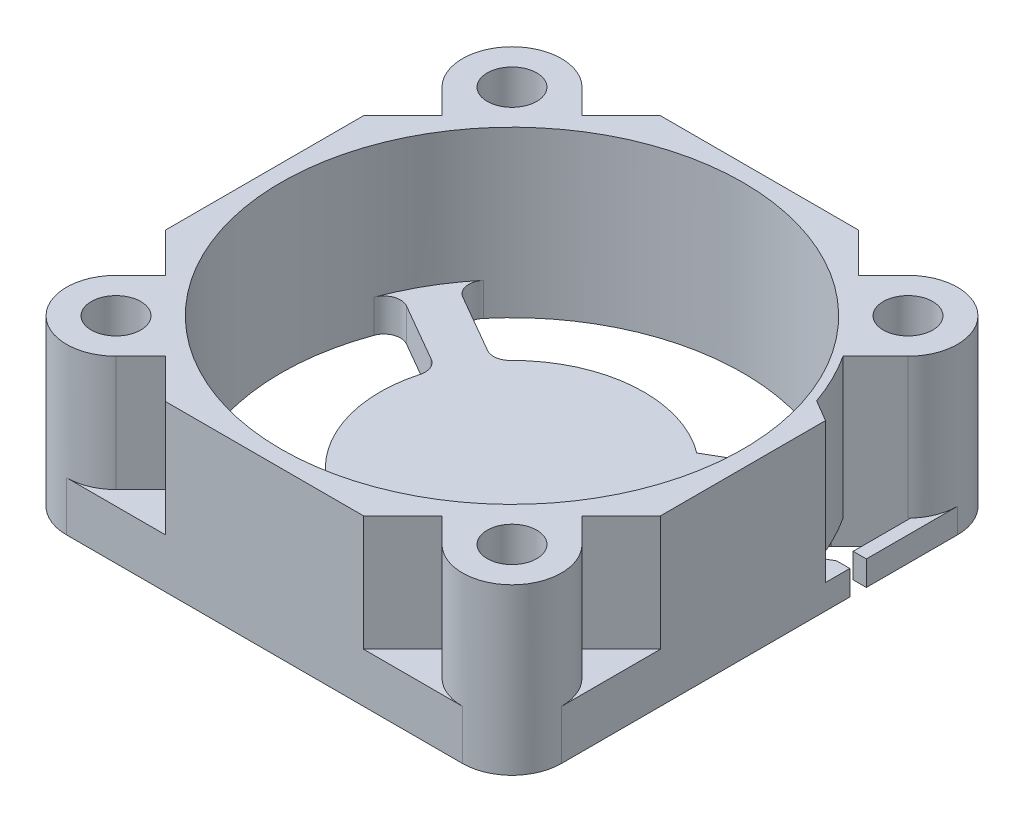
SolidWorks part; units mm, degrees
ref_plane "前基準面" through (0, 0, 0) normal (0, 0, 1) x (1, 0, 0)
ref_plane "上基準面" through (0, 0, 0) normal (0, 1, 0) x (1, 0, 0)
ref_plane "右基準面" through (0, 0, 0) normal (1, 0, 0) x (0, 0, -1)
sketch "Sketch2" plane through (0, 0, 0) normal (0, 1, 0) x (1, 0, 0)
  line L1 (-15, -15) -> (15, -15)
  line L2 (-15, -15) -> (-15, 15)
  line L3 (-15, 15) -> (15, 15)
  line L4 (15, -15) -> (15, 15)
  line L5 (-15, -15) -> (15, 15) construction
  line L6 (-15, 15) -> (15, -15) construction
  point P0 (0, 0)
  dimension "D1" = 30
extrude "Boss-Extrude1" add sketch "Sketch2" along normal blind 10
sketch "Sketch3" plane through (0, 10, 0) normal (0, 1, 0) x (1, 0, 0)
  line L0 (15, -15) -> (15, 15) construction
  line L1 (15, 15) -> (-15, 15) construction
  line L2 (12, 15) -> (15, 15) construction
  line L3 (15, 15) -> (15, 12) construction
  line L10 (9.8787, 14.1213) -> (8.3787, 12.6213)
  line L11 (12, 12) -> (15, 12) construction
  line L12 (12, 12) -> (12, 15) construction
  line L13 (12, 15) -> (15, 15) construction
  line L14 (15, 12) -> (15, 15) construction
  line L15 (8.3787, 12.6213) -> (6, 15)
  line L16 (6, 15) -> (12, 15)
  line L17 (15, 15) -> (0, 0) construction
  line L18 (15, 6) -> (15, 12)
  line L19 (12.6213, 8.3787) -> (15, 6)
  line L20 (14.1213, 9.8787) -> (12.6213, 8.3787)
  circle A0 centre (12, 12) radius 1.5
  circle A9 centre (0, 0) radius 14
  arc A10 (9.6266, 10.1651) -> (10.1651, 9.6266) centre (12, 12) ccw
  arc A11 (14.1213, 9.8787) -> (9.8787, 14.1213) centre (12, 12) ccw
  circle A12 centre (12, 12) radius 3 construction
  point P16 (15, 12)
  line M5 (15, -15) -> (15, 15)
  line M6 (15, 15) -> (-15, 15)
  dimension "D1" = 3
  dimension "D3" = 3
  dimension "D5" = 6
  dimension "D4" = 1.5
  dimension "D2" = 28
extrude "Cut-Extrude1" cut sketch "Sketch3" against normal through all contours A10 A9 | A11 M5 M6 | A0 region at (14.3299, 10, -14.3299) region at (12, 10, -12) region at (-0.0002, 10, 0.0002)
extrude "Cut-Extrude5" cut sketch "Sketch3<3>" against normal blind 7 contours A11 L20 L19 M5 | A11 L15 L10 M6 region at (14.2274, 10, -8.4599) region at (8.4599, 10, -14.2274)
sketch "Sketch3<3>" plane through (0, 10, 0) normal (0, 1, 0) x (1, 0, 0) same geometry as "Sketch3"
pattern_circular "CirPattern2" count 4 every 90 about axis through (0, 0, 0) along (0, 1, 0) of "Cut-Extrude1", "Cut-Extrude5"
sketch "Sketch5" plane through (0, 0, 0) normal (0, -1, 0) x (1, 0, 0)
  line L0 (-1.25, 7.9017) -> (-1.25, 13.9441)
  line L1 (1.25, 7.9017) -> (1.25, 13.9441)
  line L2 (-1.25, 7.9017) -> (1.25, 7.9017)
  line L3 (-6.2181, -5.0334) -> (-11.4509, -8.0546)
  line L4 (-7.4681, -2.8683) -> (-12.7009, -5.8895)
  line L5 (-6.2181, -5.0334) -> (-7.4681, -2.8683)
  line L6 (4.8009, -6.3993) -> (10.2444, -9.5421)
  line L7 (14.1213, -9.8787) -> (12.6213, -8.3787) construction
  line L8 (6.5851, -4.5427) -> (11.7909, -7.5482)
  line L9 (14.1213, -9.8787) -> (12.6213, -8.3787) construction
  line L12 (6.5851, -4.5427) -> (4.8009, -6.3993)
  line L13 (12, -15) -> (-12, -15) construction
  line L14 (12.6213, -8.3787) -> (11.7909, -7.5482) construction
  circle A0 centre (0, 0) radius 8
  arc A2 (-1.25, 13.9441) -> (1.25, 13.9441) centre (0, 0) cw
  arc A3 (-11.4509, -8.0546) -> (-12.7009, -5.8895) centre (0, 0) cw
  circle A4 centre (0, 0) radius 14 construction
  arc A5 (10.2444, -9.5421) -> (11.7909, -7.5482) centre (0, 0) ccw
  point P9 (0, 7.9017)
  point P17 (-6.8431, -3.9509)
  dimension "D1" = 2.5
  dimension "D2" = 16
  dimension "D4" = 30
  dimension "D5" = 2.5
  dimension "D6" = 120
  dimension "D3" = 2
extrude "Boss-Extrude2" add sketch "Sketch5" against normal blind 2 contours A0 L6 L8 | A0 | L3 A3 L4 L5 | L0 A2 L1 L2 region at (8.3968, 0, -7.0427)
sketch "Sketch13" plane through (0, 0, 0) normal (0, -1, 0) x (1, 0, 0)
  line L0 (8.4675, -8.5162) -> (11.7175, -2.8871)
  line L1 (4.8009, -6.3993) -> (10.2444, -9.5421) construction
  line L2 (11.7175, -2.8871) -> (13.4496, -3.8871)
  line L3 (8.4675, -8.5162) -> (10.2444, -9.5421)
  arc A0 (11.7909, -7.5482) -> (1.25, 13.9441) centre (0, 0) ccw construction
  arc A1 (10.2444, -9.5421) -> (13.4496, -3.8871) centre (0, 0) ccw
  dimension "D1" = 6.5
  dimension "D2" = 2
extrude "Boss-Extrude3" add sketch "Sketch13" against normal blind 2
fillet "Fillet1" radius 1 5 edges at (-1.25, 1, 13.9441) (1.25, 1, 13.9441) (10.2444, 1, -9.5421) (-12.7009, 1, -5.8895) (-11.4509, 1, -8.0546)
fillet "Fillet2" radius 1 4 edges at (-6.2181, 1, -5.0334) (-7.4681, 1, -2.8683) (1.25, 1, 7.9017) (-1.25, 1, 7.9017)
sketch "Sketch9" plane through (0, 0, 0) normal (0, -1, 0) x (1, 0, 0)
  line L0 (9.7175, -6.3512) -> (11.7909, -7.5482)
  line L2 (14.2, -9.9574) -> (14.2, -6.475)
  line L3 (14.2, -6.475) -> (15, -6.475)
  line L4 (15, 12) -> (15, -12) construction
  line L5 (15, -5.475) -> (15, -6.475)
  line L6 (14.1213, -9.8787) -> (12.6213, -8.3787) construction
  line L7 (15, -5.475) -> (14.2, -5.475)
  line L8 (14.2, -5.475) -> (11.2175, -3.7531)
  line L9 (14.1213, -9.8787) -> (12.6213, -8.3787)
  line L10 (12.6213, -8.3787) -> (11.7909, -7.5482)
  line L11 (11.2175, -3.7531) -> (9.7175, -6.3512)
  line L12 (13.4496, -3.8871) -> (11.7175, -2.8871) construction
  line L13 (15, 12) -> (15, -12) construction
  line L14 (14.1213, -9.8787) -> (14.2, -9.9574)
  line L15 (6.5851, -4.5427) -> (9.7175, -6.3512) construction
  dimension "D1" = 0.8
  dimension "D2" = 1
  dimension "D3" = 1
extrude "Cut-Extrude8" cut sketch "Sketch9" against normal blind 1.5 contours L9 L10 L0 L11 L8 L7 L5 L3 L2 L14
sketch "Sketch10" plane through (0, 1.5, 0) normal (0, -1, 0) x (1, 0, 0)
  line L1 (14.2, -9.9574) -> (11.7909, -7.5482) construction
  line L3 (11.7909, -7.5482) -> (14.2, -9.9574) construction
  line L4 (11.7909, -7.5482) -> (14.1213, -9.8787)
  line L5 (13.6938, -4.7675) -> (15, -4)
  line L6 (15, 12) -> (15, -5.475) construction
  line L7 (15, -4) -> (15, -12)
  line L8 (15, -6.475) -> (15, -12) construction
  line L26 (15, 12) -> (15, 6) construction
  line L27 (15, 12) -> (15, 6)
  circle A1 centre (0, 0) radius 14 construction
  circle A2 centre (0, 0) radius 14 construction
  arc A3 (12.1525, -7.9099) -> (13.6938, -4.7675) centre (0, 0) ccw
  arc A4 (9.8787, -14.1213) -> (14.1213, -9.8787) centre (12, -12) ccw construction
  arc A5 (15, -12) -> (14.1213, -9.8787) centre (12, -12) ccw
  line M62 (11.7909, -7.5482) -> (14.2, -9.9574)
  line M63 (14.2, -9.9574) -> (14.2, -6.475)
  line M64 (14.2, -6.475) -> (15, -6.475)
  line M65 (15, -6.475) -> (15, -5.475)
  line M66 (15, -5.475) -> (14.2, -5.475)
  line M67 (14.2, -5.475) -> (11.2175, -3.7531)
  dimension "D1" = 0.5
  dimension "D2" = 10
  dimension "D3" = 3.5
extrude "Cut-Extrude9" cut sketch "Sketch10" against normal through all contours A3 L4 M62 M63 M64 M65 M66 M67 | A3 L7 L5 M67 M66 | A5 L7 M64 M63 M62 region at (13.6337, 1.5, -7.2984) region at (14.6258, 1.5, -8.5644) region at (14.4393, 1.5, -4.8837)
sketch "Sketch12" plane through (0, 10, 0) normal (0, 1, 0) x (1, 0, 0)
  circle A0 centre (12.9579, 7.7429) radius 0.595
  circle A1 centre (13.532, 6.6891) radius 0.595
  arc A4 (14.2967, -0.3089) -> (7.7061, 12.046) centre (0, 0) ccw
  arc A5 (14.4966, -0.3132) -> (7.8138, 12.2145) centre (0, 0) ccw
  dimension "D1" = 1.19
  dimension "D2" = 1.19
  dimension "D5" = 14.3
  dimension "D4" = 1.2
  dimension "D3" = 0.2
sketch3d "3DSketch1"
  line L0 (12.9579, 10, -7.7429) -> (12.9579, 1.75, -7.7429)
  line L1 (12.0919, 0.75, -7.2429) -> (-0.0325, 0.75, -0.2429)
  line L2 (6.5851, 2, -4.5427) -> (9.7175, 2, -6.3512) construction
  line L3 (13.532, 10, -6.6891) -> (13.532, 1.75, -6.6891)
  line L4 (12.666, 0.75, -6.1891) -> (0.5416, 0.75, 0.8109)
  arc A1 (13.532, 1.75, -6.6891) -> (12.666, 0.75, -6.1891) centre (12.666, 1.75, -6.1891) ccw
  arc A2 (12.0919, 0.75, -7.2429) -> (12.9579, 1.75, -7.7429) centre (12.0919, 1.75, -7.2429) ccw
  spline S0 degree 3 poles (12.9579, 10, -7.7429) (12.9579, 31.1368, -7.7429) (25.284, 28.5265, -10.0814) (26.4986, 12.5375, -8.9469) (29.5585, 12.6212, -15.1035) knots 0 0 0 0 0.520984 1 1 1 1
  spline S1 degree 3 poles (13.532, 10, -6.6891) (13.532, 32.3, -6.6891) (21.7525, 28.1923, -5.0601) (27.3092, 11.3599, -3.5428) (32.6305, 11.2191, -12.8673) knots 0 0 0 0 0.445652 1 1 1 1
  point P15 (13.532, 0.75, -6.6891)
  point P16 (12.166, 1.75, -7.0552)
  point P19 (12.9579, 0.75, -7.7429)
  point P20 (12.5919, 1.75, -6.3769)
  dimension "D5" = 1
  dimension "D2" = 15
  dimension "D3" = 9.25
